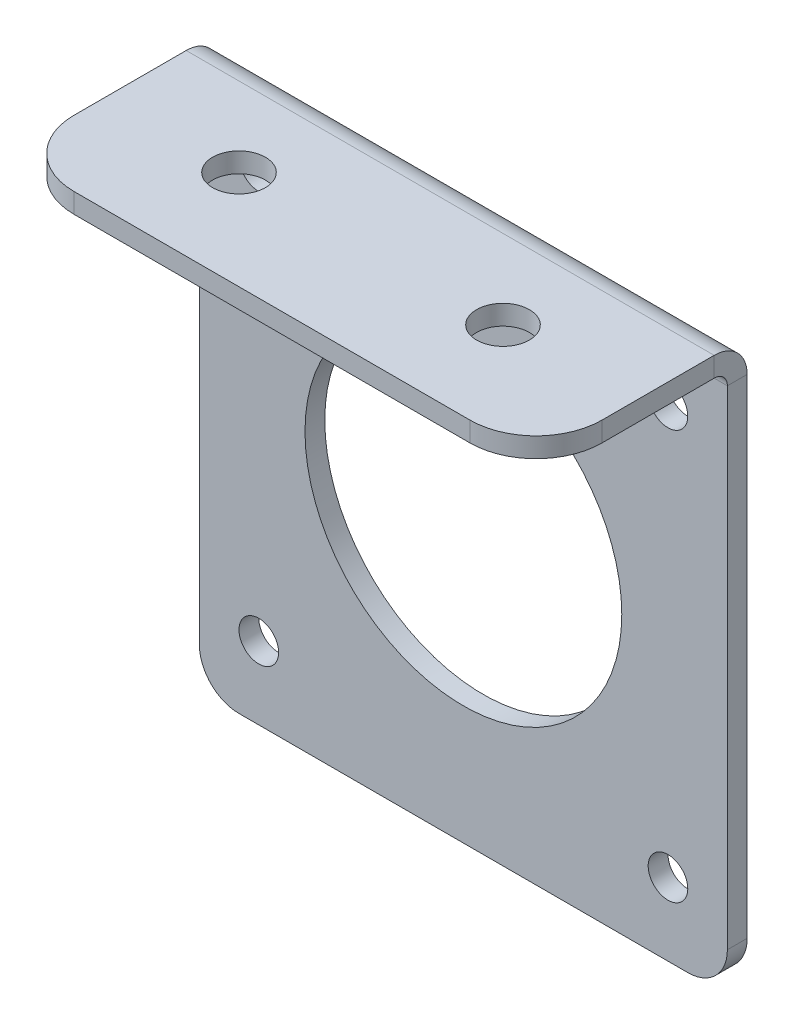
SolidWorks part; units mm, degrees
note: The reader was unsure of these and kept them because the rebuilt part matched: flange length of "边线-法兰1".
material "1023 碳钢板 (SS)"
ref_plane "前视基准面" through (0, 0, 0) normal (0, 0, 1) x (1, 0, 0)
ref_plane "上视基准面" through (0, 0, 0) normal (0, 1, 0) x (1, 0, 0)
ref_plane "右视基准面" through (0, 0, 0) normal (1, 0, 0) x (0, 0, -1)
sketch "草图1" plane through (0, 0, 0) normal (0, 0, 1) x (1, 0, 0)
  line L0 (0, 0) -> (20568.7415, 0) construction
  line L1 (0, 0) -> (0, 20568.7415) construction
  line L3 (-20, 21.5) -> (20, 21.5)
  line L4 (-20, 21.5) -> (-20, -18)
  line L5 (-17, -21) -> (17, -21)
  line L6 (20, 21.5) -> (20, -18)
  circle A0 centre (-15.5, 15.5) radius 1.5
  circle A1 centre (15.5, 15.5) radius 1.5
  circle A2 centre (15.5, -15.5) radius 1.5
  circle A3 centre (-15.5, -15.5) radius 1.5
  arc A4 (17, -21) -> (20, -18) centre (17, -18) ccw
  arc A5 (-20, -18) -> (-17, -21) centre (-17, -18) ccw
  circle A6 centre (0, 0) radius 12
  dimension "D4" = 3
  dimension "D5" = 15.5
  dimension "D6" = 15.5
  dimension "D7" = 3
  dimension "D8" = 24
  dimension "D1" = 40
  dimension "D2" = 21
  dimension "D3" = 21.5
base flange "基体-法兰1" sketch "草图1" thickness 1.5 reverse thickness direction no parameters "D1"=1
edge flange "边线-法兰1" sketch "草图8" flange angle 90 flange length 16 flange position material inside bend radius 1 thickness 1.5 relief rectangular parameters "D6"=10
sketch "草图8" plane through (0, 21.5, 0) normal (0, 1, 0) x (-1, 0, 0)
  line L0 (-20, 0) -> (20, 0) construction
  line L1 (-20, 0) -> (20, 0)
  line L2 (-20, 0) -> (-20, 9.5)
  line L3 (-15, 14.5) -> (15, 14.5)
  line L4 (20, 9.5) -> (20, 0)
  line L5 (0, 0) -> (0, 50000) construction
  arc A0 (15, 14.5) -> (20, 9.5) centre (15, 9.5) cw
  arc A1 (-20, 9.5) -> (-15, 14.5) centre (-15, 9.5) cw
  circle A2 centre (-10, 7) radius 2
  circle A3 centre (10, 7) radius 2
  point P13 (0, 0)
  dimension "D1" = 5
  dimension "D2" = 4
  dimension "D3" = 7
  dimension "D4" = 10
  dimension "D5" = 14.5
bend "边线折弯1" bend radius 1 bend angle 90 parameters "D5"=1
sketch "折弯-线1" [suppressed] plane through (0, 0, 0) normal (0, 1, 0) x (1, 0, 0)
sketch "边界框1" [suppressed] plane through (0, 0, 0) normal (0, 1, 0) x (1, 0, 0)
sheet metal parameters "钣金6" thickness 1.5 parameters "D1"=2
flat pattern "平板型式6" [suppressed]
sketch "折弯-线2" plane through (0, 0, 0) normal (0, 1, 0) x (1, 0, 0)
sketch3d "边界框2" [suppressed]
  line L0 (37, -3, 0) -> (37, 38, 0) construction
  line L1 (-3, -3, 0) -> (-3, 38, 0) construction
  line L2 (37, -3, 0) -> (-3, -3, 0) construction
  line L3 (37, 38, 0) -> (-3, 38, 0) construction
sheet metal parameters "钣金7" thickness 1.5 parameters "D1"=2
flat pattern "平板型式6"
sketch "折弯-线2" plane through (0, 0, 0) normal (0, 0, 1) x (1, 0, 0)
  line L0 (20, 20.5566) -> (-20, 20.5566) construction
  line L1 (20, 20.5566) -> (-20, 20.5566) construction
sketch3d "边界框2" [suppressed]
  line L0 (37, -3, 0) -> (37, 53.3133, 0) construction
  line L1 (-3, -3, 0) -> (-3, 53.3133, 0) construction
  line L2 (37, -3, 0) -> (-3, -3, 0) construction
  line L3 (37, 53.3133, 0) -> (-3, 53.3133, 0) construction
bend of the flat pattern "展开-<边线折弯1>1"
